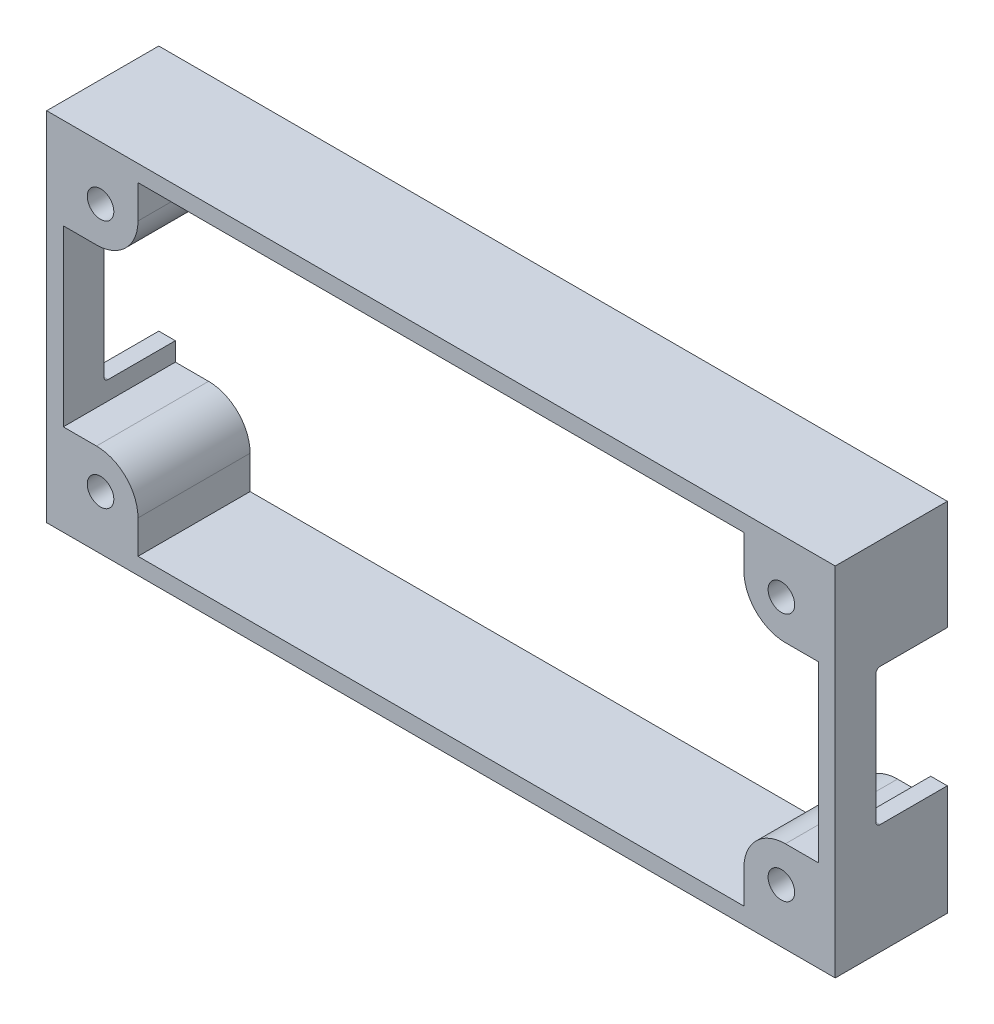
SolidWorks part; units mm, degrees
ref_plane "前视基准面" through (0, 0, 0) normal (0, 0, 1) x (1, 0, 0)
ref_plane "上视基准面" through (0, 0, 0) normal (0, 1, 0) x (1, 0, 0)
ref_plane "右视基准面" through (0, 0, 0) normal (1, 0, 0) x (0, 0, -1)
other "Configuration Table"
sketch "草图1" plane through (0, 0, 1.6001) normal (0, 0, 1) x (1, 0, 0)
  line L0 (2, -0.0127) -> (88.0002, -0.0127) construction
  line L1 (-0.4873, 0.4873) -> (90.4875, 0.4873)
  line L2 (-0.4873, 0.4873) -> (-0.4873, -38.4874)
  line L3 (-0.4873, -38.4874) -> (90.4875, -38.4874)
  line L4 (90.4875, 0.4873) -> (90.4875, -38.4874)
  line L5 (0.0127, -36.0001) -> (0.0127, -2) construction
  line L6 (89.9875, -2) -> (89.9875, -36.0001) construction
  line L7 (88.0002, -37.9874) -> (2, -37.9874) construction
  line L9 (-2.4873, 2.4873) -> (92.4875, 2.4873)
  line L10 (-2.4873, 2.4873) -> (-2.4873, -40.4874)
  line L11 (-2.4873, -40.4874) -> (92.4875, -40.4874)
  line L12 (92.4875, 2.4873) -> (92.4875, -40.4874)
  dimension "D1" = 0.5
  dimension "D2" = 0.5
  dimension "D3" = 0.5
  dimension "D4" = 0.5
  dimension "D5" = 2
  dimension "D6" = 2
  dimension "D7" = 2
  dimension "D8" = 2
extrude "凸台-拉伸1" add sketch "草图1" along normal blind 13.5
sketch "草图2" plane through (0, 0, 1.6001) normal (0, 0, 1) x (1, 0, 0)
  line L0 (90.4875, 0.4873) -> (-0.4873, 0.4873) construction
  line L1 (-0.4873, 0.4873) -> (8.5127, 0.4873)
  line L2 (-0.4873, 0.4873) -> (-0.4873, -8.5127)
  line L3 (-0.4873, -8.5127) -> (8.5127, -8.5127)
  line L4 (8.5127, 0.4873) -> (8.5127, -8.5127)
  line L6 (90.4875, 0.4873) -> (81.4875, 0.4873)
  line L7 (90.4875, 0.4873) -> (90.4875, -8.5127)
  line L8 (90.4875, -8.5127) -> (81.4875, -8.5127)
  line L9 (81.4875, 0.4873) -> (81.4875, -8.5127)
  line L10 (-0.4873, -38.4874) -> (8.5127, -38.4874)
  line L11 (-0.4873, -38.4874) -> (-0.4873, -29.4874)
  line L12 (-0.4873, -29.4874) -> (8.5127, -29.4874)
  line L13 (8.5127, -38.4874) -> (8.5127, -29.4874)
  line L14 (90.4875, -38.4874) -> (81.4875, -38.4874)
  line L15 (90.4875, -38.4874) -> (90.4875, -29.4874)
  line L16 (90.4875, -29.4874) -> (81.4875, -29.4874)
  line L17 (81.4875, -38.4874) -> (81.4875, -29.4874)
  dimension "D1" = 9
  dimension "D2" = 9
  dimension "D3" = 9
  dimension "D4" = 9
extrude "凸台-拉伸2" add sketch "草图2" along normal blind 13.5
sketch "草图3" plane through (0, 0, 1.6001) normal (0, 0, 1) x (1, 0, 0)
  circle A0 centre (4, -4) radius 1.6
  circle A1 centre (86.0002, -4) radius 1.6
  circle A2 centre (86.0002, -34.0001) radius 1.6
  circle A3 centre (4, -34.0001) radius 1.6
  dimension "D1" = 3.2
extrude "切除-拉伸1" cut sketch "草图3" along normal blind 13.5
sketch "草图4" plane through (0, 0, 1.6001) normal (0, 0, 1) x (1, 0, 0)
  line L1 (-2.4873, -10.75) -> (-0.4873, -10.75)
  line L2 (-2.4873, -10.75) -> (-2.4873, -27.25)
  line L3 (-2.4873, -27.25) -> (-0.4873, -27.25)
  line L4 (-0.4873, -10.75) -> (-0.4873, -27.25)
  line L5 (-2.4873, 2.4873) -> (-2.4873, -40.4874) construction
  line L6 (-0.4873, -8.5127) -> (-0.4873, -29.4874) construction
  line L7 (-5.15, -11.25) -> (4.5, -11.25) construction
  line L8 (90.4875, -29.4874) -> (90.4875, -8.5127) construction
  line L9 (90.4875, -10.6891) -> (92.4875, -10.6891)
  line L10 (90.4875, -10.6891) -> (90.4875, -27.1891)
  line L11 (90.4875, -27.1891) -> (92.4875, -27.1891)
  line L12 (92.4875, -10.6891) -> (92.4875, -27.1891)
  line L13 (92.4875, -40.4874) -> (92.4875, 2.4873) construction
  line L16 (87.2711, -26.6891) -> (82.7211, -26.6891) construction
  line L18 (4.5, -26.75) -> (-5.15, -26.75) construction
  line L19 (82.7211, -11.1891) -> (87.2711, -11.1891) construction
  dimension "D1" = 0.5
  dimension "D2" = 0.5
  dimension "D3" = 0.5
  dimension "D4" = 0.5
extrude "切除-拉伸2" cut sketch "草图4" along normal blind 8.6
fillet "圆角1" radius 5 4 edges at (81.4875, -29.4874, 8.3501) (8.5127, -29.4874, 8.3501) (81.4875, -8.5127, 8.3501) (8.5127, -8.5127, 8.3501)
fillet "圆角2" radius 0.5 4 edges at (91.4875, -27.1891, 10.2001) (91.4875, -10.6891, 10.2001) (-1.4873, -27.25, 10.2001) (-1.4873, -10.75, 10.2001)
